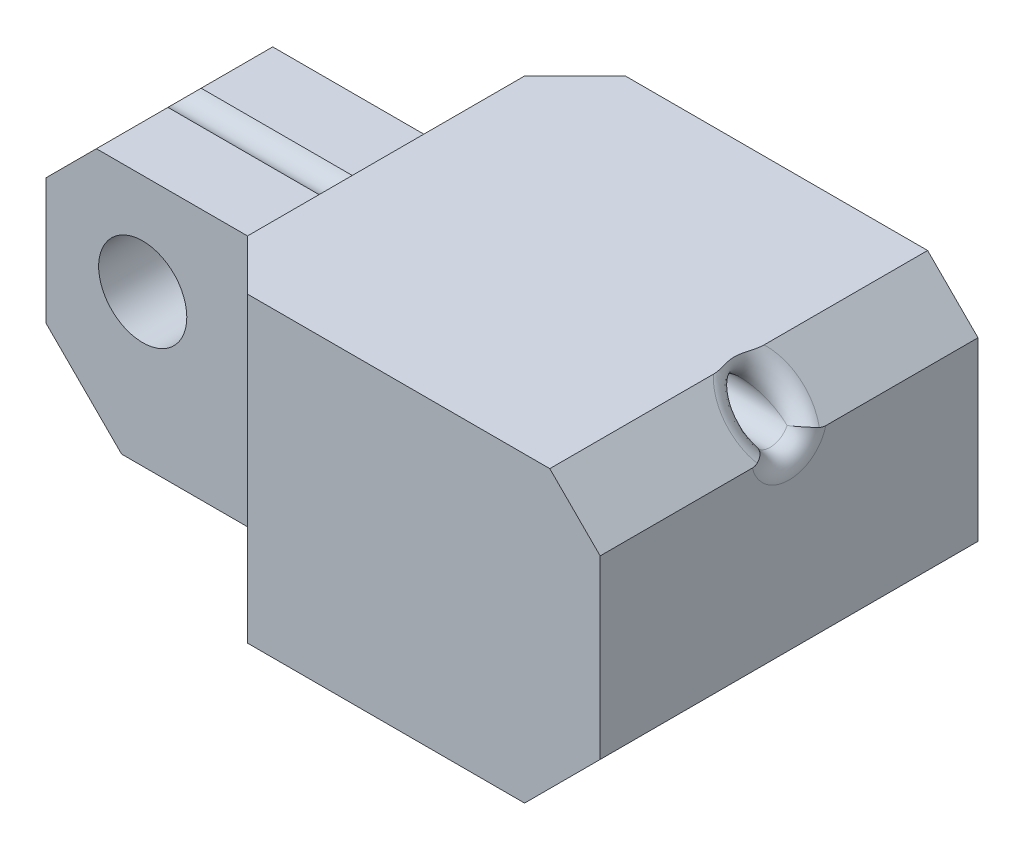
SolidWorks part; units mm, degrees
ref_plane "Спереди" through (0, 0, 0) normal (0, 0, 1) x (1, 0, 0)
ref_plane "Сверху" through (0, 0, 0) normal (0, 1, 0) x (1, 0, 0)
ref_plane "Справа" through (0, 0, 0) normal (1, 0, 0) x (0, 0, -1)
sketch "Эскиз2" plane through (0, 0, 0) normal (1, 0, 0) x (0, 0, -1)
  line L1 (-7.5, 6) -> (7.5, 6)
  line L2 (-7.5, 6) -> (-7.5, -6)
  line L3 (-7.5, -6) -> (7.5, -6)
  line L4 (7.5, 6) -> (7.5, -6)
  line L5 (-7.5, 6) -> (7.5, -6) construction
  line L6 (-7.5, -6) -> (7.5, 6) construction
  point P0 (0, 0)
extrude "Вытянуть1" add sketch "Эскиз2" along normal blind 26
sketch "Эскиз3" plane through (0, 6, 0) normal (0, 1, 0) x (1, 0, 0)
  line L0 (0, 0) -> (-9.2006, 0) construction
  line L1 (10, -9.9613) -> (10, -3.5)
  line L2 (-3.345, 9.9613) -> (10, 9.9613)
  line L3 (-3.345, 9.9613) -> (-3.345, 3.5)
  line L4 (-3.345, 3.5) -> (10, 3.5)
  line L5 (10, 9.9613) -> (10, 3.5)
  line L6 (-3.345, -9.9613) -> (10, -9.9613)
  line L7 (-3.345, -3.5) -> (10, -3.5)
  line L8 (-3.345, -9.9613) -> (-3.345, -3.5)
  line L9 (0, 7.5) -> (0, -7.5) construction
  dimension "D1" = 3.5
  dimension "D2" = 10
extrude "Вырез-Вытянуть1" cut sketch "Эскиз3" against normal through all
sketch "Эскиз4" plane through (0, 0, 3.5) normal (0, 0, 1) x (1, 0, 0)
  circle A0 centre (3.8399, 0) radius 1.75
extrude "Вытянуть2" cut sketch "Эскиз4" against normal through all
chamfer "Фаска4" distance 3 angle 45 1 edges at (26, -6, 0)
chamfer "Фаска5" distance 3 angle 45 1 edges at (0, -6, 0)
sketch "Эскиз8" plane through (0, 0, 0) normal (-1, 0, 0) x (0, 0, 1)
  line L0 (0, 6) -> (0, 2.0994) construction
  line L2 (-3.5, 6) -> (-7.5, 6) construction
  line L3 (-3.9395, 7.8642) -> (3.9729, 7.8642)
  line L4 (-3.9395, 7.8642) -> (-3.9395, 4)
  line L5 (-3.9395, 4) -> (3.9729, 4)
  line L6 (3.9729, 7.8642) -> (3.9729, 4)
  dimension "D1" = 2
extrude "Вытянуть4" cut sketch "Эскиз8" against normal blind 10
chamfer "Фаска6" distance 2 angle 45 1 edges at (0, 4, 0)
sketch "Эскиз10" plane through (26, 0, 0) normal (1, 0, 0) x (0, 0, -1)
  circle A0 centre (0, 4.3577) radius 0.75
extrude "Вырез-Вытянуть2" cut sketch "Эскиз10" against normal through all
fillet "Скругление1" radius 0.75 1 edges at (10, 5.1077, 0)
chamfer "Фаска7" distance 2 angle 45 1 edges at (26, 6, 0)
fillet "Скругление2" radius 0.75 2 edges at (26, 3.6077, 0) (24.8923, 5.1077, 0)
chamfer "Фаска8" distance 2 angle 45 2 edges at (10, 0, -7.5) (10, 0, 7.5)
